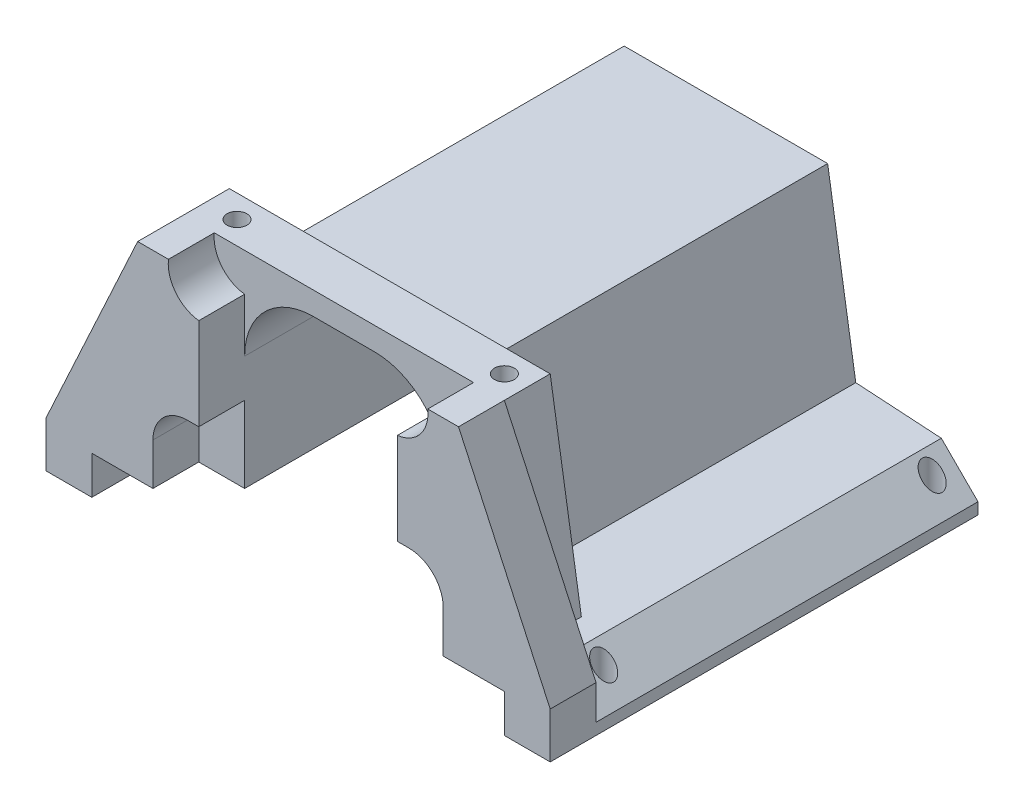
SolidWorks part; units mm, degrees
ref_plane "Front Plane" through (0, 0, 0) normal (0, 0, 1) x (1, 0, 0)
ref_plane "Top Plane" through (0, 0, 0) normal (0, 1, 0) x (1, 0, 0)
ref_plane "Right Plane" through (0, 0, 0) normal (1, 0, 0) x (0, 0, -1)
sketch "Sketch1" plane through (0, 0, 0) normal (0, 0, 1) x (1, 0, 0)
  line L0 (-33, 0) -> (-33, 32)
  line L1 (-33, 32) -> (33, 32)
  line L2 (33, 32) -> (33, 0)
  line L3 (33, 0) -> (-33, 0)
  dimension "D1" = 66
  dimension "D2" = 32
extrude "Boss-Extrude1" add sketch "Sketch1" along normal blind 56
sketch "Sketch2" plane through (0, 0, 56) normal (0, 0, 1) x (1, 0, 0)
  line L1 (-33, 0) -> (33, 0) construction
  line L2 (-13, 0) -> (13, 0)
  line L7 (-13, 0) -> (-13, 20)
  line L8 (-4, 29) -> (4, 29)
  line L9 (13, 20) -> (13, 0)
  line L13 (33, 32) -> (-33, 32) construction
  circle A0 centre (0, 19) radius 9 construction
  arc A1 (-13, 20) -> (-4, 29) centre (-4, 20) cw
  arc A2 (4, 29) -> (13, 20) centre (4, 20) cw
  dimension "D1" = 18
  dimension "D8" = 9
  dimension "D2" = 19
  dimension "D6" = 3
  dimension "D7" = 13
extrude "Cut-Extrude1" cut sketch "Sketch2" against normal up to next
sketch "Sketch4" plane through (0, 0, 56) normal (0, 0, 1) x (1, 0, 0)
  line L0 (-33, 0) -> (-13, 0) construction
  line L1 (-27, 0) -> (27, 0)
  line L2 (-27, 0) -> (-27, 5)
  line L3 (-27, 5) -> (27, 5)
  line L4 (27, 0) -> (27, 5)
  line L5 (-33, 32) -> (-33, 0) construction
  line L6 (33, 0) -> (33, 32) construction
  dimension "D1" = 6
  dimension "D2" = 6
  dimension "D3" = 5
extrude "Cut-Extrude2" cut sketch "Sketch4" against normal blind 50
sketch "Sketch5" plane through (0, 0, 0) normal (0, 0, 1) x (1, 0, 0)
  line L0 (-33, 6) -> (-17, 7)
  line L1 (-33, 32) -> (-33, 0) construction
  line L2 (-17, 7) -> (-13, 32)
  line L3 (33, 32) -> (-33, 32) construction
  line L4 (-13, 32) -> (-33, 32)
  line L5 (-33, 32) -> (-33, 6)
  line L6 (-33, 0) -> (-27, 0) construction
  line L7 (-27, 0) -> (-13, 0) construction
  line L8 (-13, 20) -> (-13, 5) construction
  dimension "D1" = 6
  dimension "D2" = 7
  dimension "D3" = 4
  dimension "D4" = 20
extrude "Cut-Extrude3" cut sketch "Sketch5" along normal offset from surface (44 mm away) 12 up to face at (0, 13.2663, 56)
mirror "Mirror1" about plane through (0, 0, 0) normal (1, 0, 0) of "Cut-Extrude3"
sketch "Sketch6" plane through (0, 32, 0) normal (0, 1, 0) x (1, 0, 0)
  line L1 (-33, 0) -> (33, 0)
  line L2 (-33, 0) -> (-33, -44)
  line L3 (-33, -44) -> (33, -44)
  line L4 (33, 0) -> (33, -44)
extrude "Cut-Extrude4" cut sketch "Sketch6" against normal blind 2
sketch "Sketch7" plane through (0, 0, 56) normal (0, 0, 1) x (1, 0, 0)
  line L0 (-12.5, 31.5) -> (12.5, 31.5) construction
  line L1 (-12.5, 36) -> (12.5, 36)
  line L2 (-12.5, 27) -> (12.5, 27)
  line L3 (-33, 0) -> (-27, 0) construction
  line L4 (-14.5, 10.5) -> (14.5, 10.5) construction
  line L5 (-14.5, 15) -> (14.5, 15)
  line L6 (-14.5, 6) -> (14.5, 6)
  circle A0 centre (-12.5, 31.5) radius 2 construction
  circle A1 centre (12.5, 31.5) radius 2 construction
  circle A2 centre (-14.5, 10.5) radius 2 construction
  circle A3 centre (14.5, 10.5) radius 2 construction
  circle A4 centre (-14.5, 10.5) radius 3.5 construction
  circle A5 centre (14.5, 10.5) radius 3.5 construction
  arc A6 (-12.5, 36) -> (-12.5, 27) centre (-12.5, 31.5) ccw
  arc A7 (12.5, 27) -> (12.5, 36) centre (12.5, 31.5) ccw
  arc A8 (-14.5, 15) -> (-14.5, 6) centre (-14.5, 10.5) ccw
  arc A9 (14.5, 6) -> (14.5, 15) centre (14.5, 10.5) ccw
  point P12 (0, 31.5)
  point P18 (0, 10.5)
  dimension "D1" = 4
  dimension "D2" = 7
  dimension "D9" = 4.5
  dimension "D3" = 25
  dimension "D4" = 29
  dimension "D5" = 21
  dimension "D6" = 31.5
  dimension "D7" = 14.5
  dimension "D8" = 12.5
extrude "Cut-Extrude5" cut sketch "Sketch7" against normal blind 6
sketch "Sketch8" plane through (0, 32, 0) normal (0, 1, 0) x (1, 0, 0)
  line L0 (-33, -44) -> (33, -44) construction
  circle A0 centre (-17, -47) radius 1.3
  circle A1 centre (18, -47) radius 1.3
  dimension "D2" = 2.6
  dimension "D1" = 35
  dimension "D3" = 17
  dimension "D4" = 3
extrude "Cut-Extrude6" cut sketch "Sketch8" against normal blind 12
sketch "Sketch9" plane through (0, 0, 56) normal (0, 0, 1) x (1, 0, 0)
  line L0 (-21, 32) -> (-33, 6)
  line L1 (-16.9721, 32) -> (-33, 32) construction
  line L3 (-33, 32) -> (-33, 0) construction
  line L4 (-33, 6) -> (-33, 32)
  line L5 (-33, 32) -> (-21, 32)
  dimension "D1" = 12
extrude "Cut-Extrude7" cut sketch "Sketch9" against normal up to next
sketch "Sketch10" plane through (0, 0, 56) normal (0, 0, 1) x (1, 0, 0)
  line L0 (-19, 10.5) -> (-19, 5)
  line L1 (-13, 5) -> (-27, 5) construction
  line L2 (-19, 5) -> (-13, 5)
  line L3 (-13, 5) -> (-13, 10.5)
  line L4 (-13, 6) -> (-13, 15) construction
  line L5 (-13, 10.5) -> (-19, 10.5)
  arc A0 (-14.5, 15) -> (-14.5, 6) centre (-14.5, 10.5) ccw construction
extrude "Cut-Extrude8" cut sketch "Sketch10" against normal up to surface (6 mm away) up to face at (-14.875, 10.5, 50)
sketch "Sketch12" plane through (0, 0, 44) normal (0, 0, -1) x (-1, 0, 0)
  line L0 (21, 32) -> (25.0808, 6.4949)
  line L1 (17, 7) -> (33, 6) construction
  line L2 (25.0808, 6.4949) -> (33, 6)
  line L3 (33, 6) -> (21, 32)
  line L4 (13.32, 30) -> (17, 7) construction
extrude "Cut-Extrude10" cut sketch "Sketch12" against normal blind 6
mirror "Mirror2" about plane through (0, 0, 0) normal (1, 0, 0) of "Cut-Extrude10", "Cut-Extrude8", "Cut-Extrude7"
sketch "Sketch11" plane through (0, 0, 56) normal (0, 0, 1) x (1, 0, 0)
  line L0 (16.9721, 32) -> (-16.9721, 32) construction
  line L1 (-13, 20) -> (13, 20)
  line L2 (-13, 20) -> (-13, 32)
  line L3 (-13, 32) -> (13, 32)
  line L4 (13, 20) -> (13, 32)
extrude "Cut-Extrude9" cut sketch "Sketch11" against normal up to surface (6 mm away) up to face at (0, 28.6213, 50)
chamfer "Chamfer1" distance 4.5 angle 45 2 edges at (33, 6, 25) (-33, 6, 25) first distance on face at (33, 3.6, 32.4) first distance on face at (-25.0269, 6.4983, 31.3333)
sketch "Sketch13" plane through (0, 0, 0) normal (0, -1, 0) x (1, 0, 0)
  line L1 (-33, 56) -> (-27, 56) construction
  line L2 (-33, 56) -> (-33, 0) construction
  line L5 (33, 56) -> (33, 0) construction
  line L6 (13, 0) -> (33, 0) construction
  circle A0 centre (-30, 46) radius 1.3
  circle A1 centre (30, 46) radius 1.3
  circle A2 centre (30, 3) radius 1.3
  circle A3 centre (-30, 3) radius 1.3
  dimension "D1" = 2.6
  dimension "D2" = 10
  dimension "D3" = 3
  dimension "D4" = 3
  dimension "D5" = 3
extrude "Cut-Extrude11" cut sketch "Sketch13" against normal up to next
chamfer "Chamfer2" distance 5 angle 45 2 edges at (-20, 0, 6) (20, 0, 6)
